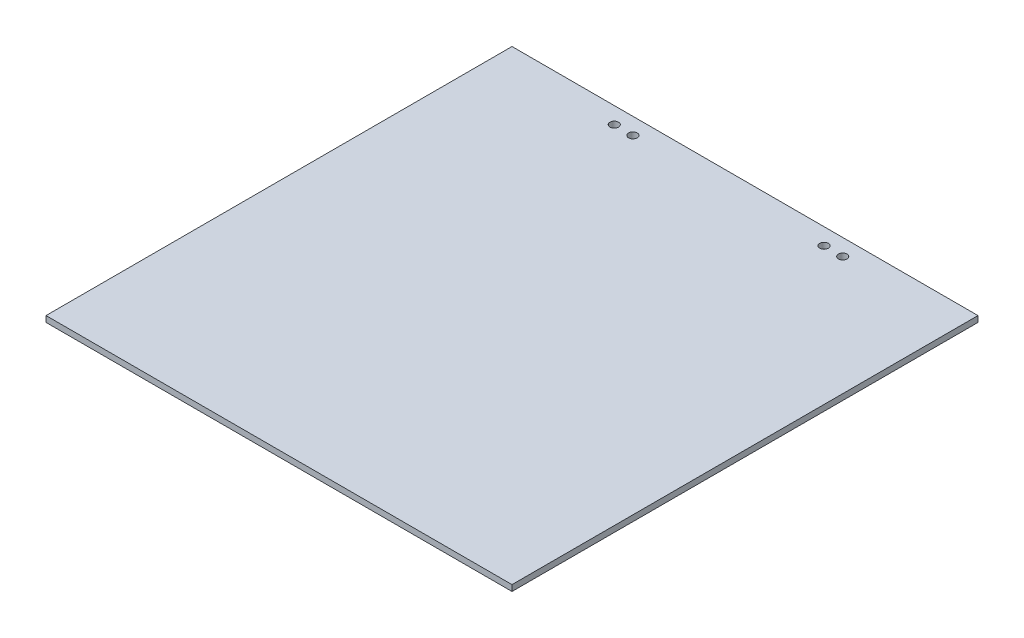
SolidWorks part; units mm, degrees
ref_plane "Front Plane" through (0, 0, 0) normal (0, 0, 1) x (1, 0, 0)
ref_plane "Top Plane" through (0, 0, 0) normal (0, 1, 0) x (1, 0, 0)
ref_plane "Right Plane" through (0, 0, 0) normal (1, 0, 0) x (0, 0, -1)
sketch "Sketch1" plane through (0, 0, 0) normal (0, 1, 0) x (1, 0, 0)
  line L1 (0, 0) -> (247.65, 0)
  line L2 (0, 0) -> (0, 247.65)
  line L3 (0, 247.65) -> (247.65, 247.65)
  line L4 (247.65, 0) -> (247.65, 247.65)
  dimension "D1" = 247.65
  dimension "D2" = 247.65
extrude "Boss-Extrude1" add sketch "Sketch1" along normal blind 3.175
sketch "Sketch2" plane through (0, 3.175, 0) normal (0, 1, 0) x (1, 0, 0)
  line L0 (65.405, 238.8616) -> (70.739, 238.8616) construction
  line L1 (176.911, 238.8616) -> (182.245, 238.8616) construction
  line L2 (247.65, 247.65) -> (0, 247.65) construction
  circle A0 centre (63.119, 238.8616) radius 2.286
  circle A1 centre (73.025, 238.8616) radius 2.286
  circle A2 centre (174.625, 238.8616) radius 2.286
  circle A3 centre (184.531, 238.8616) radius 2.286
  point P14 (123.825, 247.65)
  dimension "D3" = 4.572
  dimension "D1" = 5.334
  dimension "D2" = 5.334
  dimension "D4" = 8.7884
  dimension "D5" = 50.8
  dimension "D6" = 50.8
extrude "Cut-Extrude1" cut sketch "Sketch2" against normal through all
